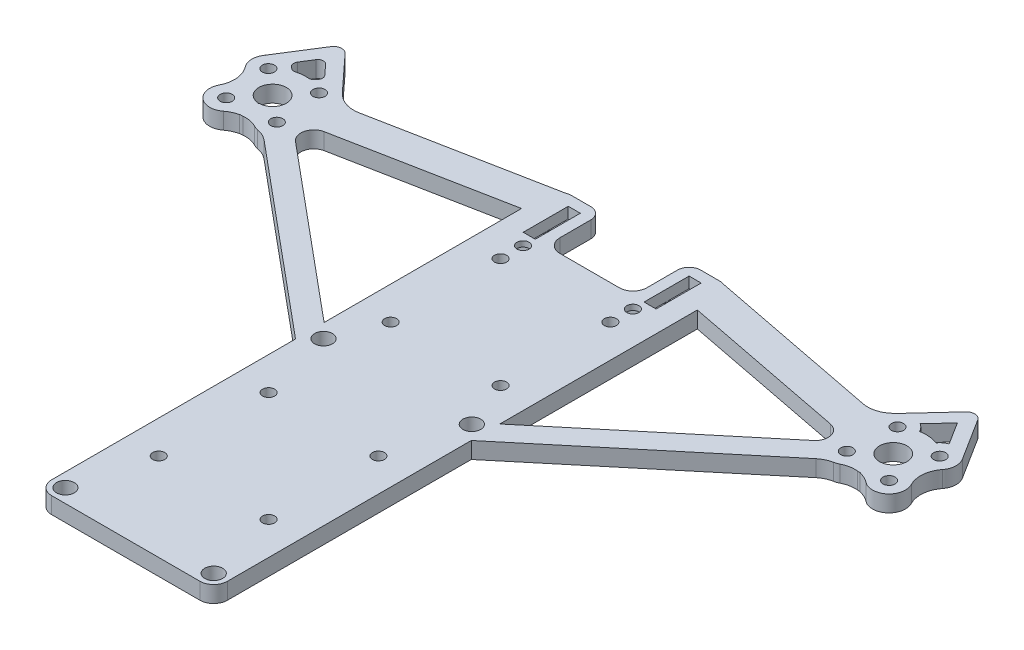
SolidWorks part; units mm, degrees
ref_plane "Front Plane" through (0, 0, 0) normal (0, 0, 1) x (1, 0, 0)
ref_plane "Top Plane" through (0, 0, 0) normal (0, 1, 0) x (1, 0, 0)
ref_plane "Right Plane" through (0, 0, 0) normal (1, 0, 0) x (0, 0, -1)
sketch "Sketch1" plane through (0, 0, 0) normal (0, 1, 0) x (1, 0, 0)
  line L0 (0, 42.225) -> (0, -42.225) construction
  line L1 (16, 42.225) -> (-16, 42.225)
  line L2 (16, 42.225) -> (16, -42.225)
  line L3 (16, -42.225) -> (-16, -42.225)
  line L4 (-16, 42.225) -> (-16, -42.225)
  line L5 (16, 42.225) -> (-16, -42.225) construction
  line L6 (16, -42.225) -> (-16, 42.225) construction
  line L12 (-12.1, 50.425) -> (-12.1, 52.425) construction
  line L17 (-11, 52.425) -> (-11, 42.225) construction
  line L18 (-7.9, 42.225) -> (-14.1, 42.225)
  line L20 (-10, 36) -> (10, 36)
  line L21 (-10, 36) -> (-10, 16)
  line L22 (-10, 16) -> (10, 16)
  line L23 (10, 36) -> (10, 16)
  line L24 (-10, 36) -> (10, 16) construction
  line L25 (-10, 16) -> (10, 36) construction
  line L26 (-14.5, 10.775) -> (14.5, 10.775)
  line L27 (-14.5, 10.775) -> (-14.5, 41.225)
  line L28 (-14.5, 41.225) -> (14.5, 41.225)
  line L29 (14.5, 10.775) -> (14.5, 41.225)
  line L30 (-14.5, 10.775) -> (14.5, 41.225) construction
  line L31 (-14.5, 41.225) -> (14.5, 10.775) construction
  line L32 (-10, -6.225) -> (10, -6.225)
  line L33 (-10, -6.225) -> (-10, -26.225)
  line L34 (-10, -26.225) -> (10, -26.225)
  line L35 (10, -6.225) -> (10, -26.225)
  line L36 (-10, -6.225) -> (10, -26.225) construction
  line L37 (-10, -26.225) -> (10, -6.225) construction
  line L38 (-15.75, -36.225) -> (15.75, -36.225)
  line L39 (-15.75, -36.225) -> (-15.75, 3.775)
  line L40 (-15.75, 3.775) -> (15.75, 3.775)
  line L41 (15.75, -36.225) -> (15.75, 3.775)
  line L42 (-15.75, -36.225) -> (15.75, 3.775) construction
  line L43 (-15.75, 3.775) -> (15.75, -36.225) construction
  line L48 (-7.9, 42.225) -> (-7.9, 52.425)
  line L49 (-7.9, 52.425) -> (-14.1, 52.425)
  line L59 (-14.1, 42.225) -> (-14.1, 52.425)
  line L63 (-12.1, 50.425) -> (-9.9, 50.425)
  line L64 (-12.1, 50.425) -> (-12.1, 42.225)
  line L65 (-12.1, 42.225) -> (-9.9, 42.225)
  line L66 (-9.9, 50.425) -> (-9.9, 42.225)
  line L67 (-12.1, 50.425) -> (-9.9, 42.225) construction
  line L68 (-12.1, 42.225) -> (-9.9, 50.425) construction
  line L69 (-12.1, 50.425) -> (-14.1, 50.425) construction
  line L74 (7.9, 42.225) -> (14.1, 42.225)
  line L75 (14.1, 42.225) -> (14.1, 52.425)
  line L76 (7.9, 52.425) -> (14.1, 52.425)
  line L77 (7.9, 42.225) -> (7.9, 52.425)
  line L78 (12.1, 50.425) -> (9.9, 50.425)
  line L79 (12.1, 50.425) -> (12.1, 42.225)
  line L80 (12.1, 42.225) -> (9.9, 42.225)
  line L81 (9.9, 50.425) -> (9.9, 42.225)
  line L82 (-14.5, 10.775) -> (-14.5, 3.775) construction
  line L83 (-14.5, 7.275) -> (16, 7.275) construction
  line L89 (-13.5, -37.225) -> (-16, -37.225) construction
  line L94 (-14.1, 52.425) -> (-16, 52.425)
  line L95 (-14.1, 52.425) -> (-14.1, 42.225)
  line L96 (-14.1, 42.225) -> (-16, 42.225)
  line L97 (-16, 52.425) -> (-16, 42.225)
  line L98 (14.1, 52.425) -> (16, 52.425)
  line L99 (14.1, 52.425) -> (14.1, 42.225)
  line L100 (14.1, 42.225) -> (16, 42.225)
  line L101 (16, 52.425) -> (16, 42.225)
  circle A3 centre (-10, 36) radius 1.1
  circle A4 centre (10, 36) radius 1.1
  circle A5 centre (10, 16) radius 1.1
  circle A6 centre (-10, 16) radius 1.1
  circle A7 centre (-10, -6.225) radius 1.1
  circle A8 centre (10, -6.225) radius 1.1
  circle A9 centre (10, -26.225) radius 1.1
  circle A10 centre (-10, -26.225) radius 1.1
  circle A37 centre (-13.5, 7.275) radius 2.5
  circle A38 centre (-13.5, 7.275) radius 1.625
  circle A39 centre (13.5, 7.275) radius 1.625
  circle A40 centre (-13.5, -39.725) radius 2.5
  circle A41 centre (-13.5, -39.725) radius 1.625
  circle A42 centre (13.5, -39.725) radius 1.625
  point P0 (0, 0)
  point P8 (0, 0)
  point P16 (0, 26)
  point P26 (0, 26)
  point P31 (0, -16.225)
  point P36 (0, -16.225)
  point P61 (-11, 46.325)
  dimension "D3" = 2
  dimension "D17" = 2.2
  dimension "D22" = 5
  dimension "D23" = 3.25
  dimension "D8" = 32
  dimension "D9" = 22
  dimension "D10" = 20
  dimension "D11" = 29
  dimension "D12" = 30.45
  dimension "D13" = 40
  dimension "D14" = 31.5
  dimension "D15" = 1
  dimension "D16" = 7
  dimension "D18" = 2.2
  dimension "D20" = 8.2
  dimension "D24" = 1
extrude "Base shape" add sketch "Sketch1" along normal blind 2 contours L63 L66 L1 L48 L49 L59 L18 L64 | L81 L78 L79 L1 L75 L76 L77 | L94 L97 L1 L59 | L101 L98 L75 L1 | L1 L4 L3 L2 | A4 | A3 | A7 | A8 | A9 | A10 | A5 | A6 | A39 | A38 | A41 | A42 region at (15.05, 0, -47.325) region at (13.1, 0, -42.3444) region at (-8.9, 0, -42.3444) region at (-15.05, 0, -47.325)
sketch "Sketch2" plane through (0, 0, 0) normal (0, -1, 0) x (1, 0, 0)
  line L0 (-12.1, -42.225) -> (-9.9, -50.425) construction
  line L1 (12.1, -42.225) -> (9.9, -50.425) construction
  line L4 (12.1, -42.225) -> (9.9, -42.225)
  line L5 (12.1, -50.425) -> (12.1, -42.225)
  line L6 (9.9, -50.425) -> (12.1, -50.425)
  line L7 (9.9, -42.225) -> (9.9, -50.425)
  line L8 (12.1, -42.225) -> (9.9, -42.225)
  line L9 (12.1, -50.425) -> (12.1, -42.225)
  line L10 (9.9, -50.425) -> (12.1, -50.425)
  line L11 (9.9, -42.225) -> (9.9, -50.425)
  line L12 (-9.9, -42.225) -> (-12.1, -42.225)
  line L13 (-9.9, -50.425) -> (-9.9, -42.225)
  line L14 (-12.1, -50.425) -> (-9.9, -50.425)
  line L15 (-12.1, -42.225) -> (-12.1, -50.425)
  line L16 (-9.9, -42.225) -> (-12.1, -42.225)
  line L17 (-9.9, -50.425) -> (-9.9, -42.225)
  line L18 (-12.1, -50.425) -> (-9.9, -50.425)
  line L19 (-12.1, -42.225) -> (-12.1, -50.425)
  circle A0 centre (-11, -46.325) radius 1.1
  circle A1 centre (11, -46.325) radius 1.1
  dimension "D1" = 0
  dimension "D2" = 0
extrude "Camera mount pockets" add sketch "Sketch2" against normal offset from surface (1 mm away) 1 contours A0 L19 | A0 L17 | A1 L9 | A1 L11 region at (11, 0, -43.8523) region at (11, 0, -48.7977) region at (-11, 0, -43.8523) region at (-11, 0, -48.7977) up to face at (11, 2, -46.325)
fillet "Main fillets" radius 2.5 6 edges at (7.9, 1, -42.225) (-7.9, 1, -42.225) (-16, 1, -52.425) (16, 1, -52.425) (-16, 1, 42.225) (16, 1, 42.225)
fillet "Inner camera mount fillets" radius 2.1 2 edges at (-7.9, 1, -52.425) (7.9, 1, -52.425)
sketch "Sketch3" plane through (0, 2, 0) normal (0, 1, 0) x (1, 0, 0)
  line L6 (12.1, 42.225) -> (12.1, 50.425)
  line L7 (9.9, 42.225) -> (12.1, 42.225)
  line L8 (-10, 52.425) -> (-13.5, 52.425)
  line L9 (-16, 49.925) -> (-16, -39.725)
  line L10 (-13.5, -42.225) -> (13.5, -42.225)
  line L11 (16, -39.725) -> (16, 49.925)
  line L12 (13.5, 52.425) -> (10, 52.425)
  line L13 (7.9, 50.325) -> (7.9, 44.725)
  line L14 (5.4, 42.225) -> (-5.4, 42.225)
  line L15 (-7.9, 44.725) -> (-7.9, 50.325)
  line L16 (-10, 52.425) -> (-13.5, 52.425)
  line L17 (-16, 49.925) -> (-16, -39.725)
  line L18 (-13.5, -42.225) -> (13.5, -42.225)
  line L19 (16, -39.725) -> (16, 49.925)
  line L20 (13.5, 52.425) -> (10, 52.425)
  line L21 (7.9, 50.325) -> (7.9, 44.725)
  line L22 (5.4, 42.225) -> (-5.4, 42.225)
  line L23 (-7.9, 44.725) -> (-7.9, 50.325)
  line L24 (9.9, 50.425) -> (9.9, 42.225)
  line L25 (12.1, 50.425) -> (9.9, 50.425)
  line L26 (12.1, 42.225) -> (12.1, 50.425)
  line L27 (9.9, 42.225) -> (12.1, 42.225)
  line L28 (9.9, 50.425) -> (9.9, 42.225)
  line L29 (12.1, 50.425) -> (9.9, 50.425)
  line L30 (-9.9, 42.225) -> (-9.9, 50.425)
  line L31 (-12.1, 42.225) -> (-9.9, 42.225)
  line L32 (-12.1, 50.425) -> (-12.1, 42.225)
  line L33 (-9.9, 50.425) -> (-12.1, 50.425)
  line L34 (-9.9, 42.225) -> (-9.9, 50.425)
  line L35 (-12.1, 42.225) -> (-9.9, 42.225)
  line L36 (-12.1, 50.425) -> (-12.1, 42.225)
  line L37 (-9.9, 50.425) -> (-12.1, 50.425)
  circle A0 centre (13.5, -39.725) radius 1.625 construction
  circle A1 centre (-13.5, -39.725) radius 1.625 construction
  circle A2 centre (-13.5, 7.275) radius 1.625 construction
  circle A3 centre (-10, -6.225) radius 1.1 construction
  circle A4 centre (-10, -26.225) radius 1.1 construction
  circle A5 centre (10, -26.225) radius 1.1 construction
  circle A6 centre (10, -6.225) radius 1.1 construction
  circle A7 centre (13.5, 7.275) radius 1.625 construction
  arc A8 (-13.5, 52.425) -> (-16, 49.925) centre (-13.5, 49.925) ccw
  arc A9 (-16, -39.725) -> (-13.5, -42.225) centre (-13.5, -39.725) ccw
  arc A10 (13.5, -42.225) -> (16, -39.725) centre (13.5, -39.725) ccw
  arc A11 (16, 49.925) -> (13.5, 52.425) centre (13.5, 49.925) ccw
  arc A12 (-7.9, 50.325) -> (-10, 52.425) centre (-10, 50.325) ccw
  arc A13 (5.4, 42.225) -> (7.9, 44.725) centre (5.4, 44.725) ccw
  arc A14 (-7.9, 44.725) -> (-5.4, 42.225) centre (-5.4, 44.725) ccw
  arc A15 (-7.9, 50.325) -> (-10, 52.425) centre (-10, 50.325) ccw
  arc A16 (-13.5, 52.425) -> (-16, 49.925) centre (-13.5, 49.925) ccw
  arc A17 (-16, -39.725) -> (-13.5, -42.225) centre (-13.5, -39.725) ccw
  arc A18 (13.5, -42.225) -> (16, -39.725) centre (13.5, -39.725) ccw
  arc A19 (16, 49.925) -> (13.5, 52.425) centre (13.5, 49.925) ccw
  arc A21 (5.4, 42.225) -> (7.9, 44.725) centre (5.4, 44.725) ccw
  arc A22 (-7.9, 44.725) -> (-5.4, 42.225) centre (-5.4, 44.725) ccw
  circle A24 centre (-10, 16) radius 1.1 construction
  circle A25 centre (-10, 36) radius 1.1 construction
  circle A26 centre (10, 36) radius 1.1 construction
  circle A27 centre (10, 16) radius 1.1 construction
  circle A28 centre (10, 16) radius 1.1
  circle A29 centre (10, 36) radius 1.1
  circle A30 centre (-10, 36) radius 1.1
  circle A31 centre (-10, 16) radius 1.1
  circle A32 centre (13.5, 7.275) radius 1.625
  circle A33 centre (10, -6.225) radius 1.1
  circle A34 centre (10, -26.225) radius 1.1
  circle A35 centre (-10, -26.225) radius 1.1
  circle A36 centre (-10, -6.225) radius 1.1
  circle A37 centre (13.5, -39.725) radius 1.625
  circle A38 centre (-13.5, -39.725) radius 1.625
  circle A39 centre (-13.5, 7.275) radius 1.625
  arc A48 (10, 52.425) -> (7.9, 50.325) centre (10, 50.325) ccw
  arc A49 (10, 52.425) -> (7.9, 50.325) centre (10, 50.325) ccw
  dimension "D1" = 0
  dimension "D2" = 0
  dimension "D3" = 0
extrude "Thicker base" add sketch "Sketch3" along normal blind 1
sketch "Sketch4" plane through (0, 0, 0) normal (0, -1, 0) x (1, 0, 0)
  line L0 (0, 13.9568) -> (0, -8.6953) construction
  line L1 (-14.1, -38.5) -> (-5.9, -38.5)
  line L2 (-14.1, -38.5) -> (-14.1, -41.7)
  line L3 (-14.1, -41.7) -> (-5.9, -41.7)
  line L4 (-5.9, -38.5) -> (-5.9, -41.7)
  line L5 (-10, -38.5) -> (-10, -41.7) construction
  line L7 (14.1, -38.5) -> (5.9, -38.5)
  line L8 (14.1, -38.5) -> (14.1, -41.7)
  line L9 (14.1, -41.7) -> (5.9, -41.7)
  line L10 (5.9, -38.5) -> (5.9, -41.7)
  line L11 (-14.1, -38.5) -> (-10.9, -41.7) construction
  line L12 (-14.1, -40.1) -> (-5.9, -40.1) construction
  circle A0 centre (-10, -36) radius 2
  circle A1 centre (-13.3929, -39.2071) radius 1
  circle A2 centre (-13.3929, -40.9929) radius 1
  circle A3 centre (-6.6071, -39.2071) radius 1
  circle A4 centre (-6.6071, -40.9929) radius 1
  circle A5 centre (6.6071, -40.9929) radius 1
  circle A6 centre (6.6071, -39.2071) radius 1
  circle A7 centre (13.3929, -39.2071) radius 1
  circle A8 centre (13.3929, -40.9929) radius 1
  point P9 (-10, -38)
  dimension "D5" = 4
  dimension "D7" = 2
  dimension "D1" = 8.2
  dimension "D2" = 3.2
  dimension "D3" = 10
  dimension "D4" = 0.5
  dimension "D6" = 45
extrude "Battery holder pockets" cut sketch "Sketch4" against normal offset from surface (2 mm away) 1 contours A2 L2 | A2 L3 | L2 A1 | L1 A1 | A3 L4 | A3 L1 | L4 A4 | L3 A4 | A5 L9 | A5 L10 | L10 A6 | L7 A6 | A7 L7 | A7 L8 | L8 A8 | L9 A8 | L3 L4 L1 L2 | L9 L10 L7 L8 region at (-13.3929, 0, -38.3812) region at (-14.2188, 0, -39.2071) region at (-6.6071, 0, -38.3812) region at (-14.2188, 0, -40.9929) region at (-5.7812, 0, -39.2071) region at (-13.3929, 0, -41.8188) region at (-6.6071, 0, -41.8188) region at (-5.7812, 0, -40.9929) region at (14.2188, 0, -39.2071) region at (13.3929, 0, -38.3812) region at (6.6071, 0, -38.3812) region at (14.2188, 0, -40.9929) region at (5.7812, 0, -39.2071) region at (13.3929, 0, -41.8188) region at (6.6071, 0, -41.8188) region at (5.7812, 0, -40.9929) up to face at (-13.5, 3, 41.35)
sketch "Sketch5" plane through (0, 2, 0) normal (0, -1, 0) x (1, 0, 0)
  line L0 (-10, -38.5) -> (-10, -41.7) construction
  line L1 (-12.6858, -38.5) -> (-7.3142, -38.5) construction
  line L2 (-12.6858, -41.7) -> (-7.3142, -41.7) construction
  line L3 (0, 5.9884) -> (0, -5.6723) construction
  circle A0 centre (-10, -40.1) radius 1.1
  circle A1 centre (10, -40.1) radius 1.1
  dimension "D1" = 2.2
extrude "Battery holder holes" cut sketch "Sketch5" against normal up to next
sketch "Sketch6" [suppressed] plane through (0, 0, 0) normal (0, -1, 0) x (1, 0, 0)
  line L0 (0, -5.1) -> (0, 9.653) construction
  line L8 (-13.5, -7.275) -> (13.5, -7.275) construction
  line L10 (-16, -23.775) -> (16, -23.775) construction
  line L11 (-16, -49.925) -> (-16, 39.725) construction
  line L12 (16, -49.925) -> (16, 39.725) construction
  line L13 (17.5, -32.275) -> (19, -32.275)
  line L14 (16, -35.275) -> (19, -35.275)
  line L15 (16, -35.275) -> (16, -12.275)
  line L16 (16, -12.275) -> (19, -12.275)
  line L17 (19, -35.275) -> (19, -12.275)
  line L18 (16, -35.275) -> (19, -12.275) construction
  line L19 (16, -12.275) -> (19, -35.275) construction
  line L20 (16, -33.775) -> (17.5, -33.775)
  line L21 (16, -33.775) -> (16, -13.775)
  line L22 (16, -13.775) -> (17.5, -13.775)
  line L23 (17.5, -33.775) -> (17.5, -13.775)
  line L24 (16, -33.775) -> (17.5, -13.775) construction
  line L25 (16, -13.775) -> (17.5, -33.775) construction
  line L26 (17.5, -15.275) -> (19, -15.275)
  line L27 (-17.5, -32.275) -> (-19, -32.275)
  line L28 (-17.5, -15.275) -> (-19, -15.275)
  line L29 (-16, -33.775) -> (-16, -13.775)
  line L30 (-16, -33.775) -> (-17.5, -33.775)
  line L31 (-17.5, -33.775) -> (-17.5, -13.775)
  line L32 (-16, -13.775) -> (-17.5, -13.775)
  line L33 (-16, -35.275) -> (-16, -12.275)
  line L34 (-16, -35.275) -> (-19, -35.275)
  line L35 (-19, -35.275) -> (-19, -12.275)
  line L36 (-16, -12.275) -> (-19, -12.275)
  line L37 (16, 20.725) -> (19, 20.725)
  line L38 (16, 20.725) -> (16, -2.275)
  line L39 (16, -2.275) -> (19, -2.275)
  line L40 (19, 20.725) -> (19, -2.275)
  line L41 (16, 19.225) -> (17.5, 19.225)
  line L42 (16, 19.225) -> (16, -0.775)
  line L43 (16, -0.775) -> (17.5, -0.775)
  line L44 (17.5, 19.225) -> (17.5, -0.775)
  line L45 (17.5, 0.725) -> (19, 0.725)
  line L46 (17.5, 17.725) -> (19, 17.725)
  line L47 (-17.5, 17.725) -> (-19, 17.725)
  line L48 (-17.5, 0.725) -> (-19, 0.725)
  line L49 (-16, 19.225) -> (-16, -0.775)
  line L50 (-16, 19.225) -> (-17.5, 19.225)
  line L51 (-17.5, 19.225) -> (-17.5, -0.775)
  line L52 (-16, -0.775) -> (-17.5, -0.775)
  line L53 (-16, 20.725) -> (-16, -2.275)
  line L54 (-16, 20.725) -> (-19, 20.725)
  line L55 (-19, 20.725) -> (-19, -2.275)
  line L56 (-16, -2.275) -> (-19, -2.275)
  point P19 (17.5, -23.775)
  point P25 (16.75, -23.775)
  line M18 (16, -49.925) -> (16, 39.725)
  line M22 (-16, 39.725) -> (-16, -49.925)
  dimension "D1" = 10
  dimension "D4" = 23
  dimension "D5" = 3
  dimension "D6" = 1.5
  dimension "D7" = 20
  dimension "D8" = 1.5
extrude "Strap holders" [suppressed] add sketch "Sketch6" against normal up to surface (2 mm away) contours L23 L20 L14 L17 L13 M18 | L23 L26 L17 L16 L22 M18 | L45 L44 L43 L39 L40 M18 | L44 L46 L40 L37 L38 L41 | L54 L55 L47 L51 L50 M22 | L56 L52 L51 L48 L55 M22 | L36 L35 L28 L31 L32 M22 | L35 L34 L30 L31 L27 M22 up to face at (-10, 2, -41.2)
fillet "Strap holder fillets" [suppressed] radius 0.75
sketch "Sketch7" plane through (0, 3, 0) normal (0, 1, 0) x (1, 0, 0)
  line L0 (-56.5, 41) -> (-16, 48.8822) construction
  line L1 (56.5, -41) -> (-56.5, -41)
  line L2 (56.5, -41) -> (56.5, 41)
  line L3 (56.5, 41) -> (-56.5, 41)
  line L4 (-56.5, -41) -> (-56.5, 41)
  line L5 (56.5, -41) -> (-56.5, 41) construction
  line L6 (56.5, 41) -> (-56.5, -41) construction
  line L7 (-16, 49.925) -> (-16, -39.725) construction
  line L8 (-55.9269, 38.0553) -> (-15.4269, 45.9374)
  line L9 (-48.7441, 45.5657) -> (-13.5, 52.425)
  line L10 (-57.0731, 43.9447) -> (-16.5731, 51.8269) construction
  line L11 (-13.5, 7.275) -> (13.5, 7.275) construction
  line L12 (-62.2591, 34.0839) -> (-50.7409, 47.9161) construction
  line L13 (-56.5, 41) -> (-16, 7.275) construction
  line L14 (-57.7798, 39.4631) -> (-17.2798, 5.7381)
  line L15 (-55.2202, 42.5369) -> (-14.7202, 8.8119)
  line L16 (-17.2798, 5.7381) -> (-16, 4.6724)
  line L17 (-56.5, 41) -> (-61.1107, 44.8394) construction
  line L18 (-56.5, 50) -> (-56.5, 32) construction
  line L19 (-61.1107, 44.8394) -> (-52.6606, 45.6107) construction
  line L20 (-56.8857, 45.2251) -> (-57.6128, 53.192) construction
  line L21 (-58.8813, 53.9926) -> (-63.553, 46.5906)
  line L22 (-56.5103, 54.209) -> (-50.5757, 47.7751)
  line L23 (-57.4765, 51.6982) -> (-60.0373, 47.6408)
  line L24 (-57.4765, 51.6982) -> (-54.2235, 48.1715)
  circle A0 centre (-56.5, 41) radius 38.1
  circle A1 centre (-56.5, 41) radius 9
  circle A2 centre (-56.5, 41) radius 6
  circle A3 centre (-52.6606, 45.6107) radius 1.1
  circle A4 centre (-60.3394, 36.3893) radius 1.1
  circle A5 centre (-61.1107, 44.8394) radius 1.1
  circle A6 centre (-51.8893, 37.1606) radius 1.1
  circle A7 centre (-61.1107, 44.8394) radius 3
  circle A8 centre (-52.6606, 45.6107) radius 3
  circle A9 centre (-60.3394, 36.3893) radius 3
  circle A10 centre (-51.8893, 37.1606) radius 3
  circle A12 centre (-56.5, 41) radius 2.5
  circle A13 centre (-57.6128, 53.192) radius 1.5
  circle A14 centre (-67.319, 40.0125) radius 4.864
  circle A15 centre (-55.5125, 30.181) radius 4.864
  circle A16 centre (-46.7947, 50.9004) radius 4.864
  circle A17 centre (-53.3325, 29.4302) radius 4.864
  circle A18 centre (-45.6353, 37.6419) radius 2.3718
  point P0 (0, 0)
  point P36 (-51.8893, 37.1606)
  point P54 (-57.4765, 51.6982)
  arc M23 (-13.5, 52.425) -> (-16, 49.925) centre (-13.5, 49.925) ccw
  line M24 (-16, 49.925) -> (-16, -39.725)
  dimension "D3" = 76.2
  dimension "D4" = 12
  dimension "D5" = 3
  dimension "D10" = 2.2
  dimension "D11" = 5
  dimension "D12" = 3
  dimension "D1" = 113
  dimension "D2" = 82
  dimension "D13" = 8
  dimension "D6" = 3
  dimension "D7" = 3
  dimension "D8" = 2
  dimension "D9" = 2
extrude "Motor mounts" add sketch "Sketch7" against normal up to surface (3 mm away) contours A13 | A13 L21 A1 L23 | A13 L24 A1 L22 | A12 L15 L3 A2 A8 A7 A9 L4 L14 | A10 L14 L4 A2 | A12 L4 L14 A10 L15 L3 | A12 L3 L15 | A10 A2 L3 L15 | A7 L23 A1 | A8 A1 L24 | A14 A2 A7 | A14 A9 A2 | A15 L4 A2 A9 | A15 A10 A2 | A8 A2 L3 A1 | A16 A1 L9 | A1 L3 L8 A0 L9 | A10 L8 A1 L3 A2 | A10 L15 A1 L8 | A10 A1 L15 | A10 L14 A1 | A17 A1 L14 A10 | A1 L14 A0 L15 | A17 L14 A1 | A0 L14 L16 L15 M24 | A0 L8 L9 M24 M23 | A1 L8 L3 | A18 L8 A1 | A18 A1 L15 | A7 | A5 | A8 | A3 | A10 | A6 | A9 | A4 region at (-33.1819, 3, -45.6059) region at (-17.512, 3, -48.8664) region at (-21.642, 3, -11.8743) region at (-38.4384, 3, -25.9598) region at (-48.3887, 3, -46.1037) region at (-50.8649, 3, -33.6569) region at (-45.287, 3, -40.5598) region at (-57.4374, 3, -34.7934) region at (-49.1442, 3, -43.1485) region at (-51.5106, 3, -34.0266) region at (-50.7815, 3, -34.2612) region at (-48.0479, 3, -36.9785) region at (-49.0457, 3, -40.2446) region at (-47.3222, 3, -39.4546) region at (-62.4345, 3, -38.9796) region at (-57.2467, 3, -35.6949) region at (-54.8114, 3, -50.9666) region at (-48.8372, 3, -36.5961) region at (-48.5353, 3, -38.5539) region at (-51.6653, 3, -40.5782) region at (-55.689, 3, -36.374) region at (-54.4796, 3, -35.0655) region at (-57.6128, 3, -53.192) region at (-53.9078, 3, -49.0743) region at (-54.4455, 3, -39.1872) region at (-53.806, 3, -41.1887) region at (-59.9651, 3, -50.4962) region at (-62.7022, 3, -41.9126) region at (-60.5112, 3, -48.4716) up to face at (10, 0, -40.1)
fillet "Fillet2" radius 1 5 edges at (-54.2235, 1.5, -48.1715) (-55.3727, 1.5, -46.8931) (-58.6756, 1.5, -46.5917) (-60.0373, 1.5, -47.6408) (-57.4765, 1.5, -51.6982)
mirror "Mirror1" about plane through (0, 0, 0) normal (1, 0, 0) of "Motor mounts"
